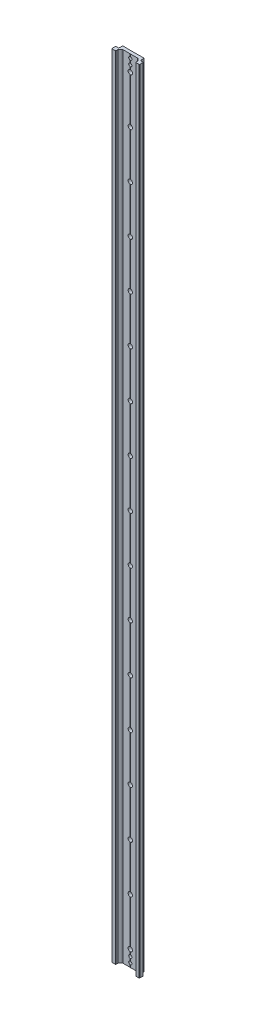
SolidWorks part; units mm, degrees
ref_plane "Plan de face" through (0, 0, 0) normal (0, 0, 1) x (1, 0, 0)
ref_plane "Plan de dessus" through (0, 0, 0) normal (0, 1, 0) x (1, 0, 0)
ref_plane "Plan de droite" through (0, 0, 0) normal (1, 0, 0) x (0, 0, -1)
ref_plane "Plan1" through (0, 500, 0) normal (0, 1, 0) x (1, 0, 0)
sketch "Esquisse1" plane through (0, 500, 0) normal (0, 1, 0) x (1, 0, 0)
  line L0 (-7.4, 4.9) -> (-7.5, 5)
  line L1 (-7.5, 5) -> (-13.2, 5)
  line L2 (-13.2, 5) -> (-13.5, 4.7)
  line L3 (-13.5, 4.7) -> (-13.5, 1.6284)
  line L4 (-14.0858, 0.2142) -> (-14.3, 0)
  line L5 (-14.3, 0) -> (-17, 0)
  line L6 (-17, 0) -> (-17.5, -0.5)
  line L7 (-17.5, -0.5) -> (-17.5, -4.5)
  line L8 (-17.5, -4.5) -> (-17, -5)
  line L9 (-17, -5) -> (-13, -5)
  line L10 (-13, -5) -> (-12.5, -4.5)
  line L11 (-12.5, -4.5) -> (-12.5, -1.8)
  line L12 (-12.5, -1.8) -> (-10.1394, 0.5607)
  line L13 (-9.0787, 1) -> (-0.25, 1)
  line L14 (-0.25, 1) -> (0, 1.1443)
  line L15 (0, 1.1443) -> (0.25, 1)
  line L16 (0.25, 1) -> (9.0787, 1)
  line L17 (10.1394, 0.5607) -> (12.5, -1.8)
  line L18 (12.5, -1.8) -> (12.5, -4.5)
  line L19 (12.5, -4.5) -> (13, -5)
  line L20 (13, -5) -> (17, -5)
  line L21 (17, -5) -> (17.5, -4.5)
  line L22 (17.5, -4.5) -> (17.5, -0.5)
  line L23 (17.5, -0.5) -> (17, 0)
  line L24 (17, 0) -> (14.3, 0)
  line L25 (14.3, 0) -> (14.0858, 0.2142)
  line L26 (13.5, 1.6284) -> (13.5, 4.7)
  line L27 (13.5, 4.7) -> (13.2, 5)
  line L28 (13.2, 5) -> (7.5, 5)
  line L29 (7.5, 5) -> (7.4, 4.9)
  line L30 (7.4, 4.9) -> (-7.4, 4.9)
  arc A0 (-13.5, 1.6284) -> (-14.0858, 0.2142) centre (-15.5, 1.6284) cw
  arc A1 (-10.1394, 0.5607) -> (-9.0787, 1) centre (-9.0787, -0.5) cw
  arc A2 (9.0787, 1) -> (10.1394, 0.5607) centre (9.0787, -0.5) cw
  arc A3 (14.0858, 0.2142) -> (13.5, 1.6284) centre (15.5, 1.6284) cw
extrude "Boss.-Extru.1" add sketch "Esquisse1" against normal blind 1000
hole_wizard "Diamètre du perçage Ø5.5 (5.5)1" positions "Esquisse3" profile "Esquisse2" hole size "Ø5.5" standard "Ansi Metric"
sketch "Esquisse3" plane through (0, 0, -4.9) normal (0, 0, -1) x (-1, 0, 0)
  point P0 (0, 420)
  point P1 (0, 480)
  point P2 (0, -480)
  point P3 (0, -420)
  point P4 (0, -360)
  point P5 (0, -300)
  point P6 (0, -240)
  point P7 (0, -180)
  point P8 (0, -120)
  point P9 (0, -60)
  point P10 (0, 0)
  point P11 (0, 60)
  point P12 (0, 120)
  point P13 (0, 180)
  point P14 (0, 240)
  point P15 (0, 300)
  point P16 (0, 360)
sketch "Esquisse2" plane through (0, 420, -4.9) normal (1, 0, 0) x (0, 1, 0)
  line L0 (0, 0) -> (0, 9.9)
  line L1 (0, 9.9) -> (2.75, 9.9)
  line L2 (2.75, 9.9) -> (2.75, 0)
  line L5 (2.75, 0) -> (0, 0)
  line L11 (0, -6.35) -> (0, 107.95) construction
  dimension "Diamètre du perçage jusqu'au prochain" = 5.5
  dimension "Profondeur du perçage jusqu'au prochain" = 9.9
sketch "Esquisse5" plane through (0, 0, -4.9) normal (0, 0, -1) x (-1, 0, 0)
  line L0 (-7.4, -500) -> (7.4, -500) construction
  line L1 (-7.4, 500) -> (7.4, 500) construction
  line L2 (7.4, -500) -> (7.4, 500) construction
  line L4 (-7.4, -500) -> (-7.4, 500) construction
  circle A0 centre (0, -495) radius 2
  circle A1 centre (0, -488) radius 2
  circle A2 centre (0, 488) radius 2
  circle A3 centre (0, 495) radius 2
  dimension "D1" = 4
  dimension "D2" = 4
  dimension "D5" = 4
  dimension "D6" = 4
  dimension "D3" = 5
  dimension "D4" = 12
  dimension "D7" = 5
  dimension "D8" = 12
  dimension "D9" = 7.4
  dimension "D10" = 14.8
  dimension "D11" = 7.4
  dimension "D12" = 7.4
  dimension "D13" = 7.4
extrude "Enlèv. mat.-Extru.1" cut sketch "Esquisse5" against normal blind 10
